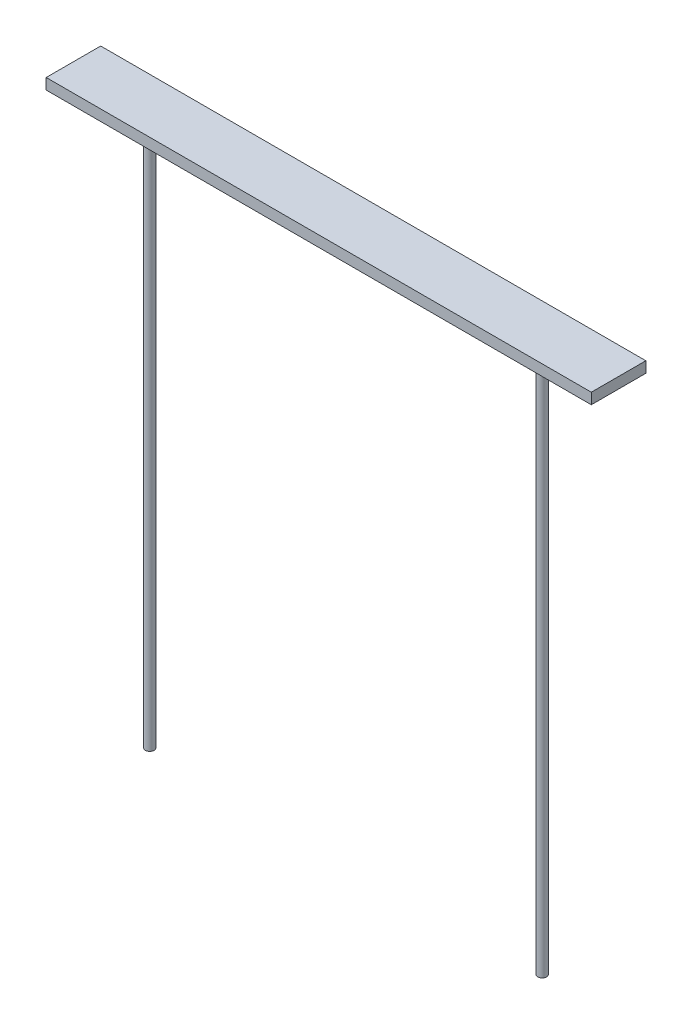
SolidWorks part; units mm, degrees
material "Stainless Steel (ferritic)"
ref_plane "Front Plane" through (0, 0, 0) normal (0, 0, 1) x (1, 0, 0)
ref_plane "Top Plane" through (0, 0, 0) normal (0, 1, 0) x (1, 0, 0)
ref_plane "Right Plane" through (0, 0, 0) normal (1, 0, 0) x (0, 0, -1)
sketch "Sketch1" plane through (0, 0, 0) normal (0, 1, 0) x (1, 0, 0)
  line L1 (-250, 25) -> (250, 25)
  line L2 (-250, 25) -> (-250, -25)
  line L3 (-250, -25) -> (250, -25)
  line L4 (250, 25) -> (250, -25)
  line L5 (-250, 25) -> (250, -25) construction
  line L6 (-250, -25) -> (250, 25) construction
  point P0 (0, 0)
extrude "Boss-Extrude1" add sketch "Sketch1" along normal blind 10
sketch "Sketch2" plane through (0, 0, 0) normal (0, -1, 0) x (1, 0, 0)
  circle A0 centre (180, 0) radius 4
extrude "Boss-Extrude2" add sketch "Sketch2" along normal blind 500
sketch "Sketch4" plane through (0, 0, 0) normal (0, -1, 0) x (1, 0, 0)
  circle A0 centre (125, 0) radius 4
sketch "Sketch6" plane through (0, 0, 0) normal (0, -1, 0) x (1, 0, 0)
  circle A0 centre (-180, 0) radius 4
extrude "Boss-Extrude3" add sketch "Sketch6" along normal blind 500
sketch "Sketch7" plane through (0, 0, 0) normal (0, -1, 0) x (-1, 0, 0)
  circle A0 centre (125, 0) radius 4
sketch "Sketch9" plane through (0, 10, 0) normal (0, 1, 0) x (1, 0, 0)
  circle A0 centre (0, 0) radius 4
  dimension "D1" = 8
